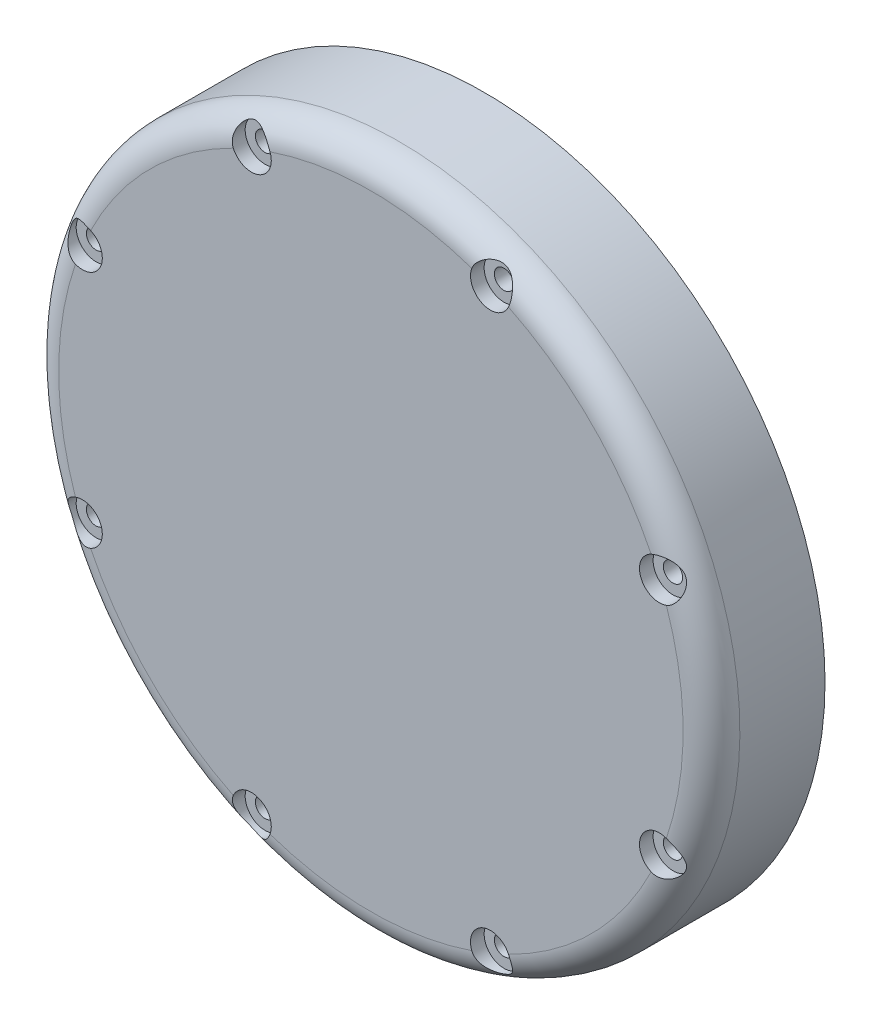
SolidWorks part; units mm, degrees
material "6063-T5"
ref_plane "Front" through (0, 0, 0) normal (0, 0, 1) x (1, 0, 0)
ref_plane "Top" through (0, 0, 0) normal (0, 1, 0) x (1, 0, 0)
ref_plane "Right" through (0, 0, 0) normal (1, 0, 0) x (0, 0, -1)
sketch "Croquis1" plane through (0, 0, 0) normal (0, 0, 1) x (1, 0, 0)
  line L0 (-15, -49.8498) -> (-15, -54.0833)
  line L1 (15, -49.8498) -> (15, -54.0833)
  line L2 (-15, -47.697) -> (15, -47.697) construction
  line L3 (0, -50) -> (0, 50) construction
  arc A0 (18.9474, -56.9298) -> (-18.9474, -56.9298) centre (0, 0) ccw
  arc A1 (16.9811, -47.0281) -> (-16.9811, -47.0281) centre (0, 0) ccw
  arc A2 (15, -54.0833) -> (18.9474, -56.9298) centre (18, -54.0833) ccw
  arc A3 (-15, -54.0833) -> (-18.9474, -56.9298) centre (-18, -54.0833) cw
  arc A4 (15, -49.8498) -> (16.9811, -47.0281) centre (18, -49.8498) cw
  arc A5 (-15, -49.8498) -> (-16.9811, -47.0281) centre (-18, -49.8498) ccw
  point P8 (0, -47.697)
  dimension "D1" = 120
  dimension "D2" = 100
  dimension "D4" = 3
  dimension "D3" = 30
extrude "Saliente-Extruir1" add sketch "Croquis1" along normal blind 15
sketch "Croquis2" plane through (0, 0, 15) normal (0, 0, 1) x (1, 0, 0)
  circle A0 centre (0, 0) radius 60
  dimension "D1" = 120
extrude "Saliente-Extruir2" add sketch "Croquis2" along normal blind 5
hole_wizard "Refrentado para tornillo con cabeza troncocónica de M31" positions "Croquis3" profile "Croquis5" counterbore size "M3" standard "Ansi Metric" end condition up to next
sketch "Croquis3" plane through (0, 0, 20) normal (0, 0, 1) x (1, 0, 0)
  line L1 (-21.0476, -50.8134) -> (21.0476, 50.8134) construction
  line L4 (0, -50) -> (0, 50) construction
  point P4 (21.0476, 50.8134)
  point P18 (50.8134, 21.0476)
  point P19 (50.8134, -21.0476)
  point P20 (21.0476, -50.8134)
  point P21 (-21.0476, -50.8134)
  point P22 (-50.8134, -21.0476)
  point P23 (-50.8134, 21.0476)
  point P24 (-21.0476, 50.8134)
  dimension "D1" = 22.5
  dimension "D2" = 110
  dimension "D3" = 8
sketch "Croquis5" plane through (-21.0476, 50.8134, 20) normal (1, 0, 0) x (0, -1, 0)
  line L0 (0, 0) -> (0, 20)
  line L1 (0, 20) -> (1.7, 20)
  line L3 (1.7, 20) -> (1.7, 2.4)
  line L4 (1.7, 2.4) -> (3.5, 2.4)
  line L5 (3.5, 2.4) -> (3.5, 0)
  line L7 (3.5, 0) -> (0, 0)
  line L11 (0, -6.35) -> (0, 107.95) construction
  dimension "Diámetro de taladro hasta el siguiente" = 3.4
  dimension "Profundidad de taladro hasta el siguiente" = 20
  dimension "Diámetro de refrentado" = 7
  dimension "Profundidad de refrentado" = 2.4
fillet "Redondeo1" radius 5 1 edges at (60, 0, 20)
